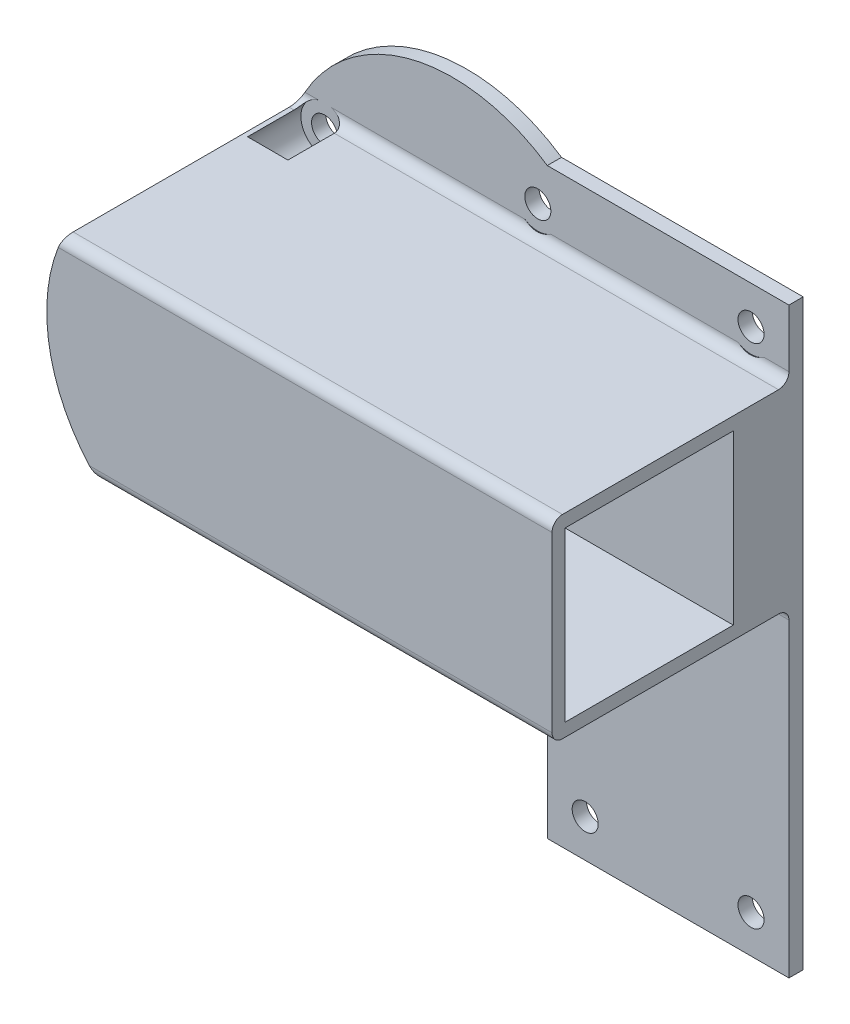
SolidWorks part; units mm, degrees
ref_plane "Front Plane" through (0, 0, 0) normal (0, 0, 1) x (1, 0, 0)
ref_plane "Top Plane" through (0, 0, 0) normal (0, 1, 0) x (1, 0, 0)
ref_plane "Right Plane" through (0, 0, 0) normal (1, 0, 0) x (0, 0, -1)
sketch "Sketch1" plane through (0, 0, 0) normal (0, 0, 1) x (1, 0, 0)
  line L0 (-35, -107) -> (0, -107) construction
  line L1 (-90, -9) -> (-90, -34) construction
  line L5 (8, 8) -> (-43, 8)
  line L6 (8, 8) -> (8, -115)
  line L7 (8, -115) -> (-43, -115)
  line L8 (-43, 8) -> (-43, -1.8875)
  line L9 (-90, -21.5) -> (-43, -21.5) construction
  line L10 (-43, -51) -> (-43, -115)
  circle A0 centre (-90, -34) radius 2.75
  circle A1 centre (-90, -9) radius 2.75
  circle A2 centre (-45, 0) radius 2.75
  circle A3 centre (0, 0) radius 2.75
  circle A4 centre (0, -107) radius 2.75
  circle A5 centre (-35, -107) radius 2.75
  arc A6 (-43, 8) -> (-43, -51) centre (-63, -21.5) ccw
  point P0 (0, 0)
  point P1 (-45, 0)
  point P3 (-90, -9)
  point P5 (-35, -107)
  point P6 (0, -107)
  point P7 (-90, -34)
  point P9 (-63, -21.5)
  dimension "D7" = 5.5
  dimension "D1" = 45
  dimension "D2" = 45
  dimension "D3" = 9
  dimension "D4" = 25
  dimension "D5" = 107
  dimension "D6" = 35
  dimension "D8" = 8
  dimension "D9" = 8
  dimension "D10" = 8
  dimension "D11" = 8
  dimension "D12" = 63
extrude "Boss-Extrude1" add sketch "Sketch1" along normal blind 3 contours A6 L10 L7 L6 L5 A2 A0 A1 A3 A4 A5 region at (-34.9713, -42.3703, 0)
sketch "Sketch4" plane through (0, 0, 3) normal (0, 0, 1) x (1, 0, 0)
  line L0 (-45, -2.75) -> (-45, -6.375) construction
  line L1 (-43, -51) -> (-43, -47.375) construction
  line L2 (8, 8) -> (8, -115) construction
  line L10 (-98.6406, -47.375) -> (8, -47.375)
  line L11 (-98.6406, -47.375) -> (-98.6406, -6.375)
  line L12 (-98.6406, -6.375) -> (8, -6.375)
  line L13 (8, -47.375) -> (8, -6.375)
  line L14 (-98.6406, -47.375) -> (8, -6.375) construction
  line L15 (-98.6406, -6.375) -> (8, -47.375) construction
  arc A1 (-43, 8) -> (-43, -51) centre (-63, -21.5) ccw construction
  circle A3 centre (-45, 0) radius 2.75 construction
  point P17 (-45.3203, -26.875)
  circle M9 centre (-90, -34) radius 2.75
  circle M10 centre (-90, -9) radius 2.75
  arc M15 (-43, 8) -> (-43, -51) centre (-63, -21.5) ccw
  line M18 (8, -115) -> (8, 8)
  dimension "D1" = 41
extrude "Boss-Extrude3" add sketch "Sketch4" along normal blind 50 contours L12 L10 M15 M18 M10 M9 | L12 M10 | M9 region at (-43.5545, -26.7001, 3) region at (-90, -9.0155, 3) region at (-90, -34, 3)
sketch "Sketch5" plane through (8, 0, 0) normal (1, 0, 0) x (0, 0, -1)
  line L0 (-53, -6.375) -> (-3, -6.375) construction
  line L1 (-50.25, -9.125) -> (-14.75, -9.125)
  line L2 (-50.25, -9.125) -> (-50.25, -44.625)
  line L3 (-50.25, -44.625) -> (-14.75, -44.625)
  line L4 (-14.75, -9.125) -> (-14.75, -44.625)
  line L5 (-50.25, -9.125) -> (-14.75, -44.625) construction
  line L6 (-32.5, -26.875) -> (-32.5, -6.375) construction
  line L8 (-14.75, -9.125) -> (-50.25, -44.625) construction
  line L9 (-53, -26.875) -> (-32.5, -26.875) construction
  line L10 (-53, -47.375) -> (-53, -6.375) construction
  dimension "D3" = 35.5
  dimension "D4" = 35.5
extrude "Cut-Extrude1" cut sketch "Sketch5" against normal through all
fillet "Fillet1" radius 2.2 4 edges at (-39.7549, -47.375, 3) (-39.7549, -47.375, 53) (-40.5902, -6.375, 3) (-43.636, -6.375, 53)
sketch "Sketch6" plane through (0, 0, 0) normal (0, 0, -1) x (-1, 0, 0)
  circle A0 centre (45, 0) radius 5
  circle A1 centre (45, 0) radius 5
  circle A2 centre (90, -9) radius 5
  circle A3 centre (90, -34) radius 5
  circle A4 centre (0, 0) radius 5
  circle M1 centre (45, 0) radius 2.75
  circle M4 centre (0, 0) radius 2.75
  dimension "D1" = 10
extrude "Cut-Extrude3" cut sketch "Sketch6" against normal blind 12 from offset 3 contours A4 M4 | A0 M1 | A2 | A3 region at (-40.1414, 0, 0) region at (4.8586, 0, 0) offset against normal yes
